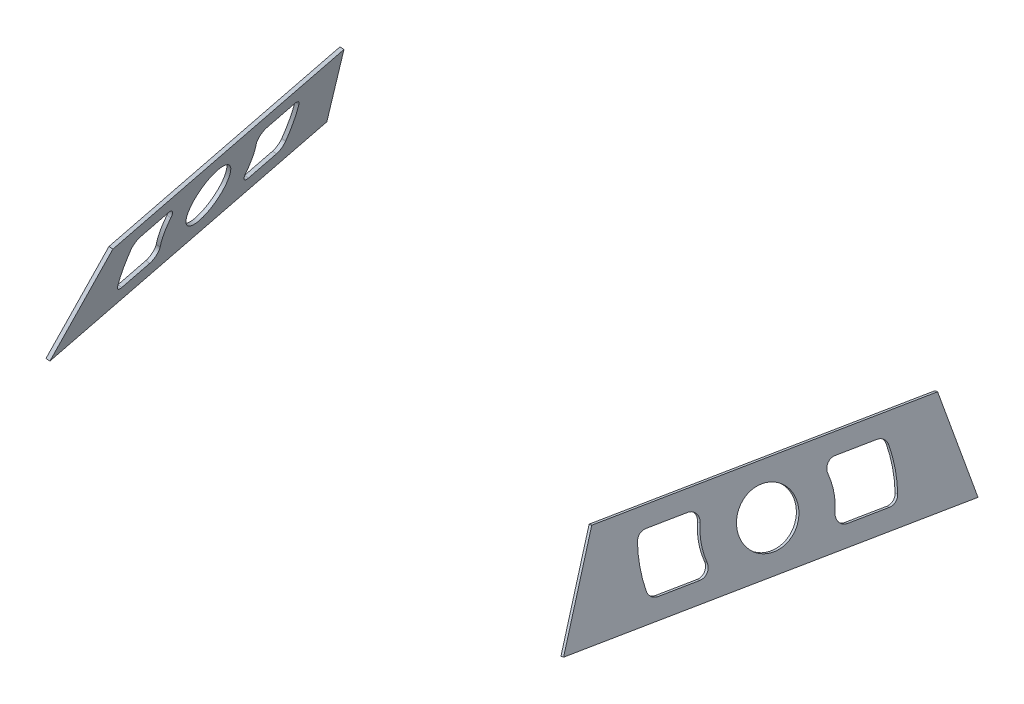
SolidWorks part; units mm, degrees
material "AISI 4130 Steel, normalized at 870C"
ref_plane "Front Plane" through (0, 0, 0) normal (0, 0, 1) x (1, 0, 0)
ref_plane "Top Plane" through (0, 0, 0) normal (0, 1, 0) x (1, 0, 0)
ref_plane "Right Plane" through (0, 0, 0) normal (1, 0, 0) x (0, 0, -1)
ref_plane "Plane1" through (-647.7275, 206.835, 128.8296) normal (0.936, -0.2989, -0.1862) x (-0.1773, 0.0566, -0.9825)
ref_plane "Plane2" through (-659.6142, 210.6307, 131.1938) normal (0.936, -0.2989, -0.1862) x (-0.1773, 0.0566, -0.9825)
sketch "Sketch1" plane through (-659.6142, 210.6307, 131.1938) normal (0.936, -0.2989, -0.1862) x (-0.1773, 0.0566, -0.9825)
  line L0 (-1393.9313, 796.4424) -> (-1387.1074, 745.9484)
  line L1 (-1387.1074, 745.9484) -> (-1589.6785, 757.9902)
  line L2 (-1589.6785, 757.9902) -> (-1562.979, 806.4913)
  line L3 (-1562.979, 806.4913) -> (-1393.9313, 796.4424)
  line L4 (-1868.8378, 250.8817) -> (-1428.3419, 1051.0671) construction
  line L10 (-1428.3419, 1051.0671) -> (-1321.2913, 258.9362) construction
  line L11 (-1544.2893, 840.4421) -> (-1398.708, 831.7881) construction
  point P4 (0, 0)
  point P5 (0, 0)
  point P7 (-1553.3095, 717.0142)
  point P12 (-1521.6143, 804.2984)
  point P20 (-1471.4987, 836.1151)
  dimension "D1" = 50
  dimension "D2" = 35
extrude "Boss-Extrude1" add sketch "Sketch1" against normal blind 2
sketch "Sketch3" plane through (-647.7275, 206.835, 128.8296) normal (0.936, -0.2989, -0.1862) x (-0.1773, 0.0566, -0.9825)
  line L0 (-1390.5193, 771.1954) -> (-1576.3287, 782.2408) construction
  line L1 (-1393.9313, 796.4424) -> (-1387.1074, 745.9484) construction
  line L2 (-1589.6785, 757.9902) -> (-1562.979, 806.4913) construction
  line L3 (-1478.4551, 801.4668) -> (-1488.3929, 751.9693) construction
  line L4 (-1562.979, 806.4913) -> (-1393.9313, 796.4424) construction
  line L5 (-1387.1074, 745.9484) -> (-1589.6785, 757.9902) construction
  circle A0 centre (-1483.424, 776.7181) radius 15
  dimension "D1" = 30
extrude "Cut-Extrude4" cut sketch "Sketch3" along normal through all both and the other way through all contours A0
sketch "Sketch5" plane through (-661.4861, 211.2284, 131.5661) normal (-0.936, 0.2989, 0.1862) x (0.3518, 0.7718, 0.5297)
  circle A0 centre (1507.3574, 801.7343) radius 19.9414 construction
  circle A1 centre (1507.3574, 801.7343) radius 19.9414
  circle A2 centre (1507.358, 801.7066) radius 14.4575 construction
  circle A3 centre (1507.358, 801.7066) radius 14.4575
split line "Split Line1" [suppressed]
sketch "Sketch6" plane through (-661.4861, 211.2284, 131.5661) normal (-0.936, 0.2989, 0.1862) x (0.1773, -0.0566, 0.9825)
  line L0 (1393.9313, 796.4424) -> (1562.979, 806.4913) construction
  line L1 (1446.5748, 789.5541) -> (1426.1168, 788.338)
  line L2 (1427.8536, 758.3882) -> (1448.2869, 759.6029)
  line L4 (1589.6785, 757.9902) -> (1387.1074, 745.9484) construction
  line L5 (1518.6631, 793.8393) -> (1539.1211, 795.0555)
  line L6 (1520.5113, 763.8962) -> (1540.9447, 765.1109)
  circle A0 centre (1483.5163, 776.6002) radius 15 construction
  arc A1 (1451.7574, 783.5012) -> (1452.7271, 766.1949) centre (1483.5163, 776.6002) ccw
  arc A2 (1421.448, 783.9334) -> (1422.6908, 762.2298) centre (1483.5163, 776.6002) ccw
  arc A3 (1515.3215, 769.9158) -> (1514.234, 787.2151) centre (1483.5163, 776.6002) ccw
  arc A4 (1545.6159, 769.537) -> (1544.2787, 791.2351) centre (1483.5163, 776.6002) ccw
  arc A5 (1520.5113, 763.8962) -> (1515.3215, 769.9158) centre (1520.2146, 768.8874) cw
  arc A6 (1540.9447, 765.1109) -> (1545.6159, 769.537) centre (1540.648, 770.1021) ccw
  arc A7 (1539.1211, 795.0555) -> (1544.2787, 791.2351) centre (1539.4178, 790.0643) cw
  arc A8 (1518.6631, 793.8393) -> (1514.234, 787.2151) centre (1518.9598, 788.8481) ccw
  arc A9 (1427.8536, 758.3882) -> (1422.6908, 762.2298) centre (1427.5569, 763.3794) cw
  arc A10 (1448.2869, 759.6029) -> (1452.7271, 766.1949) centre (1447.9902, 764.5941) ccw
  arc A11 (1451.7574, 783.5012) -> (1446.5748, 789.5541) centre (1446.8715, 784.5629) ccw
  arc A12 (1426.1168, 788.338) -> (1421.448, 783.9334) centre (1426.4135, 783.3468) ccw
  point P0 (1483.5163, 776.6002)
  point P18 (1513.2433, 763.4642)
  point P21 (1544.9958, 765.3517)
  dimension "D1" = 65
  dimension "D2" = 125
  dimension "D7" = 5
  dimension "D3" = 10
  dimension "D4" = 10
  dimension "D5" = 10
  dimension "D6" = 10
extrude "Cut-Extrude5" cut sketch "Sketch6" against normal through all both and the other way through all
mirror "Mirror5" about plane through (0, 0, 0) normal (1, 0, 0) of bodies 107
